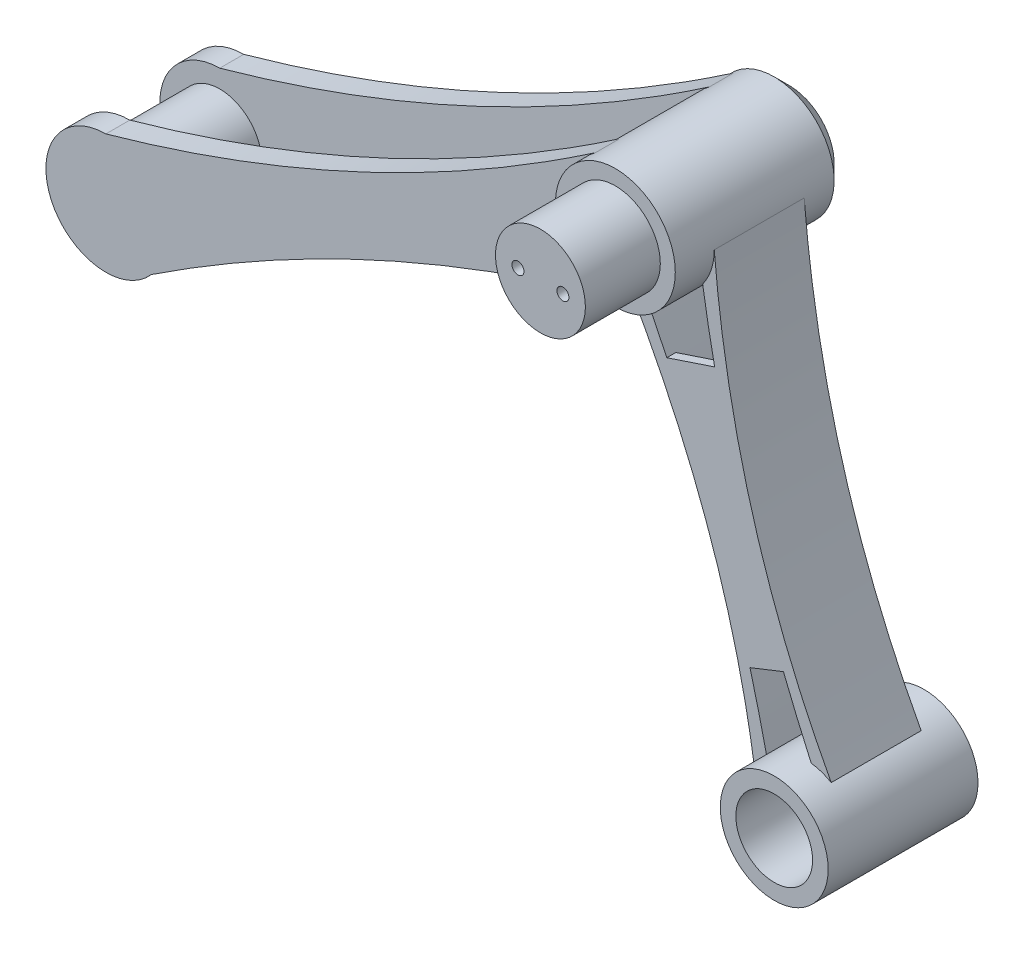
SolidWorks part; units mm, degrees
ref_plane "Front Plane" through (0, 0, 0) normal (0, 0, 1) x (1, 0, 0)
ref_plane "Top Plane" through (0, 0, 0) normal (0, 1, 0) x (1, 0, 0)
ref_plane "Right Plane" through (0, 0, 0) normal (1, 0, 0) x (0, 0, -1)
sketch "Sketch1" plane through (0, 0, 0) normal (0, 0, 1) x (1, 0, 0)
  circle A0 centre (0, 0) radius 14
extrude "Boss-Extrude1" add sketch "Sketch1" against normal blind 15 and the other way blind 15
sketch "Sketch2" plane through (0, 0, 0) normal (0, 0, 1) x (1, 0, 0)
  line L0 (0, 0) -> (175, 0) construction
  line L1 (175, 0) -> (175, 80) construction
  line L2 (175, 0) -> (225, 0) construction
  line L3 (225, 0) -> (225, -70) construction
  point P6 (0, 0)
sketch "Sketch3" plane through (0, 0, -15) normal (0, 0, -1) x (-1, 0, 0)
  circle A0 centre (0, 0) radius 20
extrude "Boss-Extrude2" add sketch "Sketch3" along normal blind 8
sketch "Sketch4" plane through (0, 0, 15) normal (0, 0, 1) x (1, 0, 0)
  circle A0 centre (0, 0) radius 20 construction
  circle A1 centre (0, 0) radius 20
extrude "Boss-Extrude3" add sketch "Sketch4" along normal blind 8
sketch "Sketch6" plane through (0, 0, 0) normal (0, 0, 1) x (1, 0, 0)
  circle A1 centre (175, 80) radius 15
extrude "Boss-Extrude5" add sketch "Sketch6" against normal blind 50 and the other way blind 15 separate body
sketch "Sketch7" plane through (0, 0, 15) normal (0, 0, 1) x (1, 0, 0)
  circle A0 centre (175, 80) radius 20
extrude "Boss-Extrude6" add sketch "Sketch7" along normal blind 10
sketch "Sketch8" plane through (0, 0, -50) normal (0, 0, -1) x (-1, 0, 0)
  line L0 (-182.5, 80) -> (-167.5, 80) construction
  circle A0 centre (-182.5, 80) radius 2
  circle A1 centre (-167.5, 80) radius 2
sketch "Sketch9" plane through (0, 0, 15) normal (0, 0, -1) x (-1, 0, 0)
  circle A0 centre (-175, 80) radius 15
  circle A1 centre (-175, 80) radius 20
extrude "Boss-Extrude7" add sketch "Sketch9" along normal blind 40
sketch "Sketch10" plane through (0, 0, 25) normal (0, 0, 1) x (1, 0, 0)
  line L0 (0, 0) -> (175, 80) construction
  line L1 (175, 80) -> (225, -70) construction
  circle A0 centre (0, 0) radius 20
  circle A1 centre (175, 80) radius 20
  circle A2 centre (225, -70) radius 18 construction
  circle A3 centre (225, -70) radius 12.8 construction
sketch "Sketch11" plane through (0, 0, 25) normal (0, 0, 1) x (1, 0, 0)
  circle A0 centre (225, -70) radius 18 construction
  circle A1 centre (225, -70) radius 18
  circle A2 centre (225, -70) radius 12.8 construction
  circle A3 centre (225, -70) radius 12.8
sketch "Sketch13" plane through (0, 0, 23) normal (0, 0, 1) x (1, 0, 0)
  line L0 (0, 0) -> (175, 80) construction
  line L1 (175, 80) -> (225, -70) construction
  circle A1 centre (175, 80) radius 20
  circle A2 centre (175, 80) radius 20
  circle A5 centre (0, 0) radius 20
  circle A6 centre (175, 80) radius 20
  spline S0 degree 2 poles (0, 20) (88.2168, 44.7305) (164.022, 96.7178) knots 0 0 0 1 1 1
  spline S1 degree 2 poles (15.1249, -13.0858) (91.5464, 37.447) (180.46, 60.7597) knots 0 0 0 1 1 1
  dimension "D1" = 0
extrude "Boss-Extrude11" add sketch "Sketch13" against normal blind 8 contours A5 S1 A6 S0 region at (88.2976, 40.3646, 23)
mirror "Mirror1" about plane through (0, 0, 0) normal (0, 0, 1) of "Boss-Extrude11"
sketch "Sketch14" plane through (0, 0, 23) normal (0, 0, 1) x (1, 0, 0)
  line L0 (175, 80) -> (225, -70) construction
  arc A0 (159, 68) -> (195, 80) centre (175, 80) ccw
  arc A1 (234.0302, -54.429) -> (208.4333, -62.9613) centre (225, -70) ccw
  spline S0 degree 2 poles (195, 80) (201.2901, 6.2444) (234.0302, -54.429) knots 0 0 0 0.710269 0.710269 0.710269
  spline S1 degree 2 poles (159, 68) (198.2212, 5.2214) (208.4333, -62.9613) knots 0 0 0 0.710269 0.710269 0.710269
sketch "Sketch15" plane through (0, 0, 0) normal (0, 0, 1) x (1, 0, 0)
  circle A0 centre (225, -70) radius 12.8
  circle A1 centre (225, -70) radius 18
extrude "Boss-Extrude12" add sketch "Sketch15" along normal blind 25 and the other way blind 25 separate body
sketch "Sketch16" plane through (0, 0, 25) normal (0, 0, 1) x (1, 0, 0)
  circle A0 centre (225, -70) radius 3.5
  circle A1 centre (225, -70) radius 12.8
extrude "Boss-Extrude13" add sketch "Sketch16" against normal blind 3
ref_plane "Plane1" through (0, 0, 15) normal (0, 0, 1) x (1, 0, 0)
sketch "Sketch17" plane through (0, 0, 15) normal (0, 0, 1) x (1, 0, 0)
  circle A0 centre (225, -70) radius 18 construction
  circle A1 centre (175, 80) radius 20 construction
  arc A2 (234.0302, -54.429) -> (208.4333, -62.9613) centre (225, -70) ccw
  arc A3 (159, 68) -> (195, 80) centre (175, 80) ccw
  parabola Q0 (195, 80) -> (234.0302, -54.429) focus (372.9824, 27.0493) apex (228.7807, -44.2735) construction
  parabola Q1 (159, 68) -> (208.4333, -62.9613) focus (48.3845, -81.15) apex (206.5395, -51.6872) construction
  parabola Q2 (195, 80) -> (234.0302, -54.429) focus (372.9824, 27.0493) apex (228.7807, -44.2735)
  parabola Q3 (159, 68) -> (208.4333, -62.9613) focus (48.3845, -81.15) apex (206.5395, -51.6872)
extrude "Boss-Extrude14" add sketch "Sketch17" against normal blind 30
sketch "Sketch18" plane through (0, 0, -15) normal (0, 0, -1) x (-1, 0, 0)
  line L0 (-175, 80) -> (-225, -70) construction
  arc A0 (-191.133, 68.1794) -> (-169.1859, 60.8637) centre (-175, 80) ccw
  arc A1 (-212.4135, -57.1322) -> (-227.3485, -52.1539) centre (-225, -70) ccw
  spline S0 degree 2 poles (-227.3485, -52.1539) (-200.8356, 6.2714) (-191.133, 68.1794) knots 0 0 0 0.776782 0.776782 0.776782
  spline S1 degree 2 poles (-212.4135, -57.1322) (-198.5687, 5.5158) (-169.1859, 60.8637) knots 0 0 0 0.776782 0.776782 0.776782
extrude "Cut-Extrude2" cut sketch "Sketch18" against normal blind 20
sketch "Sketch19" plane through (0, 0, -15) normal (0, 0, -1) x (-1, 0, 0)
  line L0 (-218.0834, -30.3399) -> (-206.9119, -34.7637)
  line L1 (-195.1238, 46.231) -> (-179.1624, 40.9105)
  parabola Q0 (-191.133, 68.1794) -> (-227.3485, -52.1539) focus (-418.5667, 92.5236) apex (-195.1238, 46.231) construction
  parabola Q1 (-195.1238, 46.231) -> (-218.0834, -30.3399) focus (-418.5667, 92.5236) apex (-195.1238, 46.231)
  parabola Q2 (-212.4135, -57.1322) -> (-169.1859, 60.8637) focus (27.3676, -56.1211) apex (-179.1624, 40.9105) construction
  parabola Q3 (-206.9119, -34.7637) -> (-179.1624, 40.9105) focus (27.3676, -56.1211) apex (-179.1624, 40.9105)
extrude "Boss-Extrude15" add sketch "Sketch19" against normal blind 3
sketch "Sketch20" plane through (0, 0, 23) normal (0, 0, 1) x (1, 0, 0)
  circle A0 centre (0, 0) radius 20 construction
  circle A1 centre (0, 0) radius 20
  circle A2 centre (175, 80) radius 20 construction
  circle A3 centre (175, 80) radius 20
extrude "Boss-Extrude16" add sketch "Sketch20" along normal blind 5
sketch "Sketch22" plane through (0, 0, -25) normal (0, 0, -1) x (-1, 0, 0)
  circle A0 centre (-225, -70) radius 12.8
  circle A1 centre (-225, -70) radius 3.5
extrude "Boss-Extrude18" add sketch "Sketch22" against normal blind 3
sketch "Sketch23" plane through (0, 0, 28) normal (0, 0, 1) x (1, 0, 0)
  circle A3 centre (175, 80) radius 15
extrude "Boss-Extrude19" add sketch "Sketch23" along normal blind 25
sketch "Sketch24" plane through (0, 0, 53) normal (0, 0, 1) x (1, 0, 0)
  line L0 (167.5, 80) -> (182.5, 80) construction
  circle A0 centre (167.5, 80) radius 2
  circle A1 centre (182.5, 80) radius 2
extrude "Cut-Extrude3" cut sketch "Sketch24" against normal blind 30
mirror "Mirror2" about plane through (0, 0, 0) normal (0, 0, 1) of "Cut-Extrude2"
mirror "Mirror3" about plane through (0, 0, 0) normal (0, 0, 1) of "Boss-Extrude15"
sketch "Sketch26" plane through (0, 0, -15) normal (0, 0, -1) x (-1, 0, 0)
  line L0 (-165.7964, 56.7052) -> (-159.4625, 67.4069)
  circle A0 centre (-175, 80) radius 20 construction
  arc A1 (-195, 80) -> (-159.4625, 67.4069) centre (-175, 80) ccw
  circle A2 centre (-225, -70) radius 18 construction
  arc A3 (-208.4333, -62.9613) -> (-234.0302, -54.429) centre (-225, -70) ccw
  parabola Q0 (-234.0302, -54.429) -> (-195, 80) focus (-372.9824, 27.0493) apex (-228.7807, -44.2735) construction
  parabola Q1 (-234.0302, -54.429) -> (-195, 80) focus (-372.9824, 27.0493) apex (-228.7807, -44.2735)
  parabola Q2 (-165.7964, 56.7052) -> (-208.4333, -62.9613) focus (-48.3845, -81.15) apex (-206.5395, -51.6872) construction
  parabola Q3 (-165.7964, 56.7052) -> (-208.4333, -62.9613) focus (-48.3845, -81.15) apex (-206.5395, -51.6872)
extrude "Boss-Extrude23" add sketch "Sketch26" against normal blind 10
sketch "Sketch27" plane through (0, 0, 25) normal (0, 0, 1) x (1, 0, 0)
  circle A0 centre (225, -70) radius 12.8
extrude "Cut-Extrude4" cut sketch "Sketch27" against normal blind 10
sketch "Sketch28" plane through (0, 0, -23) normal (0, 0, -1) x (-1, 0, 0)
  circle A0 centre (0, 0) radius 20 construction
  circle A1 centre (0, 0) radius 20
extrude "Boss-Extrude24" add sketch "Sketch28" along normal blind 5
sketch "Sketch29" plane through (0, 0, 0) normal (1, 0, 0) x (0, 0, -1)
  line L1 (-23, 20) -> (-34.3479, 20)
  line L2 (-23, 20) -> (-23, -27.4291)
  line L3 (-23, -27.4291) -> (-34.3479, -27.4291)
  line L4 (-34.3479, 20) -> (-34.3479, -27.4291)
  line L5 (25, 95) -> (59.2454, 95)
  line L6 (25, 95) -> (25, 58.5044)
  line L7 (25, 58.5044) -> (59.2454, 58.5044)
  line L8 (59.2454, 95) -> (59.2454, 58.5044)
extrude "Cut-Extrude5" cut sketch "Sketch29" against normal through all and the other way through all
sketch "Sketch30" plane through (0, 0, -25) normal (0, 0, -1) x (-1, 0, 0)
  circle A0 centre (-175, 80) radius 20
sketch "Sketch31" plane through (0, 0, -25) normal (0, 0, -1) x (-1, 0, 0)
  circle A0 centre (-175, 80) radius 20
extrude "Boss-Extrude26" add sketch "Sketch31" along normal blind 5
chamfer "Chamfer1" distance 5 angle 45 2 edges at (-20, 0, -28) (155, 80, -30)
